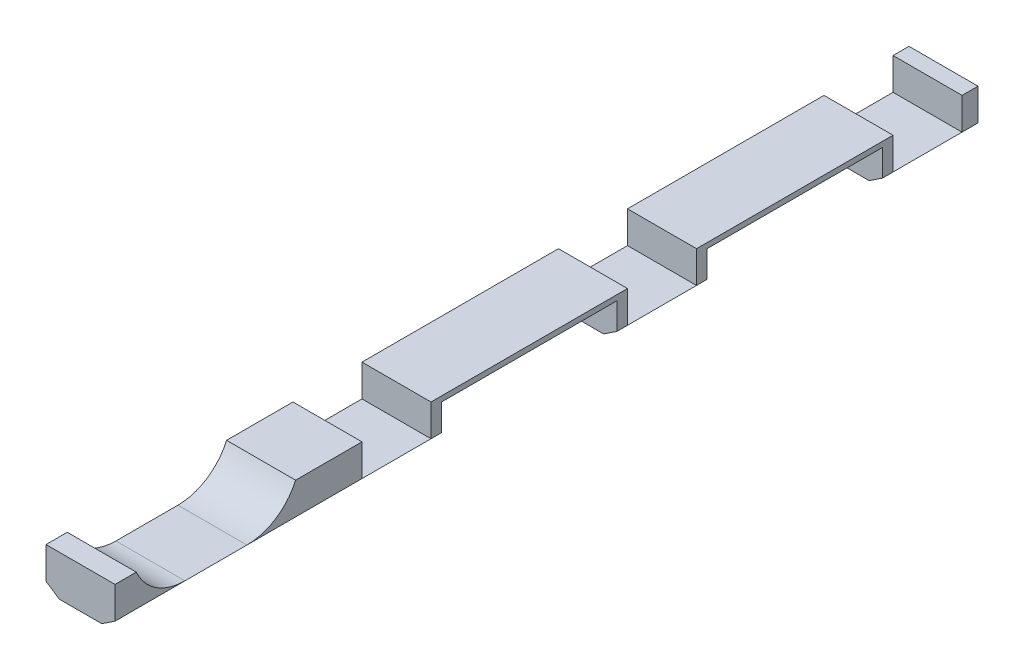
SolidWorks part; units mm, degrees
ref_plane "Front Plane" through (0, 0, 0) normal (0, 0, 1) x (1, 0, 0)
ref_plane "Top Plane" through (0, 0, 0) normal (0, 1, 0) x (1, 0, 0)
ref_plane "Right Plane" through (0, 0, 0) normal (1, 0, 0) x (0, 0, -1)
sketch "Sketch1" plane through (0, 0, 0) normal (0, 0, 1) x (1, 0, 0)
  line L0 (0, 0) -> (3.2, 0)
  line L1 (3.2, 0) -> (4.2, 0.6633)
  line L2 (4.2, 0.6633) -> (4.2, 3.0633)
  line L3 (4.2, 3.0633) -> (-1, 3.0633)
  line L4 (-1, 3.0633) -> (-1, 0.6633)
  line L5 (-1, 0.6633) -> (0, 0)
  dimension "D1" = 5.2
  dimension "D2" = 3.2
  dimension "D3" = 1.2
  dimension "D4" = 2.4
  dimension "D5" = 2.4
  dimension "D6" = 1.2
extrude "Boss-Extrude1" add sketch "Sketch1" along normal blind 65
sketch "Sketch2" plane through (-1, 0, 0) normal (-1, 0, 0) x (0, 0, 1)
  line L0 (65, 3.0633) -> (0, 3.0633) construction
  line L1 (1.2, 3.0633) -> (6.4, 3.0633)
  line L2 (1.2, 3.0633) -> (1.2, 0.6633)
  line L3 (1.2, 0.6633) -> (6.4, 0.6633)
  line L4 (6.4, 3.0633) -> (6.4, 0.6633)
  dimension "D1" = 5.2
  dimension "D2" = 2.4
  dimension "D3" = 1.2
extrude "Cut-Extrude1" cut sketch "Sketch2" against normal blind 6
pattern_linear "LPattern1" count 3 spacing 20 along (0, 0, 1) of "Cut-Extrude1"
sketch "Sketch3" plane through (-1, 0, 0) normal (-1, 0, 0) x (0, 0, 1)
  line L0 (51.4, 3.0633) -> (51.4, 0.6633)
  line L1 (65, 3.0633) -> (46.4, 3.0633) construction
  line L2 (65, 0.6633) -> (46.4, 0.6633) construction
  line L3 (51.4, 0.6633) -> (63.4, 0.6633)
  line L4 (63.4, 0.6633) -> (63.4, 3.0633)
  line L5 (63.4, 3.0633) -> (51.4, 3.0633)
  dimension "D1" = 5
  dimension "D2" = 12
extrude "Cut-Extrude2" cut sketch "Sketch3" against normal blind 6
fillet "Fillet1" radius 4 1 edges at (1.6, 0.6633, 51.4)
fillet "Fillet2" radius 4 1 edges at (1.6, 0.6633, 63.4)
sketch "Sketch5" plane through (-1, 0, 0) normal (-1, 0, 0) x (0, 0, 1)
  line L0 (21.2, 3.0633) -> (6.4, 3.0633) construction
  line L1 (7.2, 2.6633) -> (20.4, 2.6633)
  line L2 (7.2, 2.6633) -> (7.2, -0.4367)
  line L3 (7.2, -0.4367) -> (20.4, -0.4367)
  line L4 (20.4, 2.6633) -> (20.4, -0.4367)
  line L5 (6.4, 0.6633) -> (6.4, 3.0633) construction
  line L6 (21.2, 3.0633) -> (21.2, 0.6633) construction
  dimension "D1" = 0.4
  dimension "D2" = 0.8
  dimension "D3" = 0.8
  dimension "D4" = 3.1
extrude "Cut-Extrude3" cut sketch "Sketch5" against normal blind 10
pattern_linear "LPattern2" count 2 spacing 20 along (0, 0, 1) of "Cut-Extrude3"
